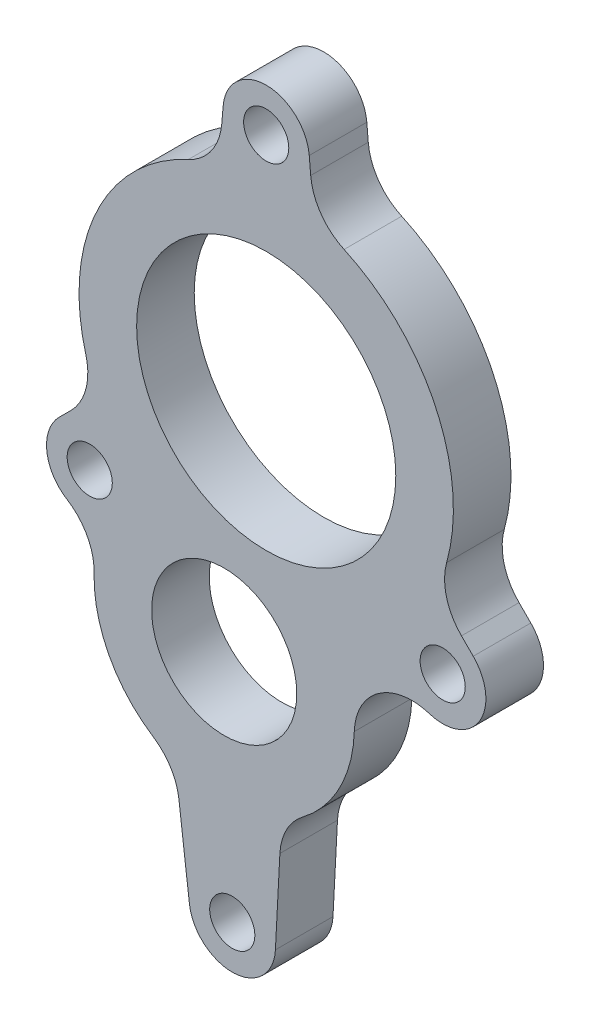
SolidWorks part; units mm, degrees
material "6061-T6 (SS)"
ref_plane "Front Plane" through (0, 0, 0) normal (0, 0, 1) x (1, 0, 0)
ref_plane "Top Plane" through (0, 0, 0) normal (0, 1, 0) x (1, 0, 0)
ref_plane "Right Plane" through (0, 0, 0) normal (1, 0, 0) x (0, 0, -1)
sketch "Sketch1" plane through (0, 0, 0) normal (0, 0, 1) x (1, 0, 0)
  line L0 (0, 0) -> (0, 25.4) construction
  line L1 (0, 0) -> (19.4575, -16.3268) construction
  line L2 (0, 0) -> (-19.4575, -16.3268) construction
  line L3 (-4.7444, 25.8151) -> (-5.2569, 19.9567)
  line L4 (4.7444, 25.8151) -> (5.2569, 19.9567)
  line L5 (22.8251, -12.9592) -> (18.6668, -8.8009)
  line L6 (16.7259, -20.228) -> (11.9087, -16.855)
  line L7 (-16.7259, -20.228) -> (-11.9087, -16.855)
  line L8 (-18.6668, -8.8009) -> (-22.8251, -12.9592)
  circle A0 centre (19.4575, -16.3268) radius 4.7625
  circle A1 centre (0, 25.4) radius 4.7625
  circle A2 centre (-19.4575, -16.3268) radius 4.7625
  circle A3 centre (19.4575, -16.3268) radius 2.4892
  circle A4 centre (-19.4575, -16.3268) radius 2.4892
  circle A5 centre (0, 25.4) radius 2.4892
  circle A6 centre (0, 0) radius 14.2875
  circle A7 centre (0, 0) radius 20.6375
  dimension "D1" = 9.525
  dimension "D4" = 4.9784
  dimension "D13" = 6.35
  dimension "D14" = 28.575
  dimension "D2" = 25.4
  dimension "D5" = 130
  dimension "D6" = 130
  dimension "D7" = 5
  dimension "D8" = 5
  dimension "D9" = 5
  dimension "D10" = 5
  dimension "D11" = 5
  dimension "D12" = 5
extrude "Boss-Extrude1" add sketch "Sketch1" along normal mid plane 6.35 contours A7 A6 | A7 L4 A1 L3 | A7 L6 A0 L5 | A7 L8 A2 L7 | A2 A4 | A1 A5 | A0 A3 | A7 A2 L7 | A7 L6 A0 | A7 A1 L3 region at (-3.9194, 21.5843, 0) region at (0, 30.0278, 0) region at (-2.5754, 19.8877, 0) region at (3.9194, 21.5843, 0) region at (-19.0539, -10.8717, 0) region at (-19.2557, -11.7034, 0) region at (-14.0152, -16.8766, 0) region at (19.0539, -10.8717, 0) region at (14.0152, -16.8766, 0) region at (23.7331, -14.5558, 0)
sketch "Sketch48" plane through (0, 0, 0) normal (0, 0, 1) x (1, 0, 0)
  line L0 (0, 0) -> (-4.6323, -26.2646) construction
  line L1 (1.0144, -51.8975) -> (1.6802, -39.1516)
  line L2 (-8.4685, -52.2302) -> (-10.0261, -39.5624)
  line L3 (-4.6323, -26.2646) -> (-3.7416, -51.649) construction
  line L4 (16.7259, -20.228) -> (11.9087, -16.855) construction
  line L5 (16.7259, -20.228) -> (11.9087, -16.855)
  circle A0 centre (-4.6323, -26.2646) radius 8
  circle A2 centre (-4.6323, -26.2646) radius 14.35
  circle A3 centre (0, 25.4) radius 2.4892 construction
  circle A4 centre (-19.4575, -16.3268) radius 2.4892 construction
  circle A5 centre (0, 0) radius 14.2875 construction
  arc A6 (-11.9087, -16.855) -> (11.9087, -16.855) centre (0, 0) ccw construction
  circle A7 centre (-19.4575, -16.3268) radius 2.4892
  circle A8 centre (0, 0) radius 14.2875
  arc A9 (-11.9087, -16.855) -> (11.9087, -16.855) centre (0, 0) ccw
  circle A10 centre (-3.7416, -51.649) radius 4.7625
  circle A11 centre (-3.7416, -51.649) radius 2.4892
  arc A12 (-22.8251, -12.9592) -> (-16.7259, -20.228) centre (-19.4575, -16.3268) ccw construction
  circle A13 centre (19.4575, -16.3268) radius 2.4892 construction
  arc A14 (9.7108, -26.7096) -> (18.0005, -20.8609) centre (16.0577, -26.9065) cw
  circle A15 centre (19.4575, -16.3268) radius 4.7625 construction
  circle A16 centre (19.4575, -16.3268) radius 4.7625
  dimension "D3" = 16
  dimension "D9" = 6.35
  dimension "D1" = 26.67
  dimension "D2" = 51.8719
  dimension "D5" = 77.1398
  dimension "D6" = 5
  dimension "D7" = 5
  dimension "D8" = 25.4
  dimension "D4" = 6.35
extrude "Boss-Extrude2" add sketch "Sketch48" along normal mid plane 6.35 contours L0 A8 A2 A7 A9 A0 | A10 L1 A2 L2 | A10 A11 | A16 L5 A9 A2 A14 region at (-4.006, -44.1148, 0) region at (-3.5793, -56.274, 0) region at (-4.1433, -40.2021, 0) region at (11.573, -20.226, 0)
extrude "Cut-Extrude1" cut sketch "Sketch48<3>" against normal through all both and the other way through all contours L0 A0 A9 | A0 L0 A9 region at (-3.4288, -19.4409, 0)
sketch "Sketch48<3>" plane through (0, 0, 0) normal (0, 0, 1) x (1, 0, 0) same geometry as "Sketch48"
fillet "Fillet1" radius 6.35 7 edges at (18.6668, -8.8009, 0) (-18.6668, -8.8009, 0) (-5.2569, 19.9567, 0) (5.2569, 19.9567, 0) (1.6802, -39.1516, 0) (-17.9144, -20.8324, 0) (-10.0261, -39.5624, 0)
equation "\"D7@Sketch48\"=\"D6@Sketch48\""
equation "\"D3@Sketch48\"=16mm"
